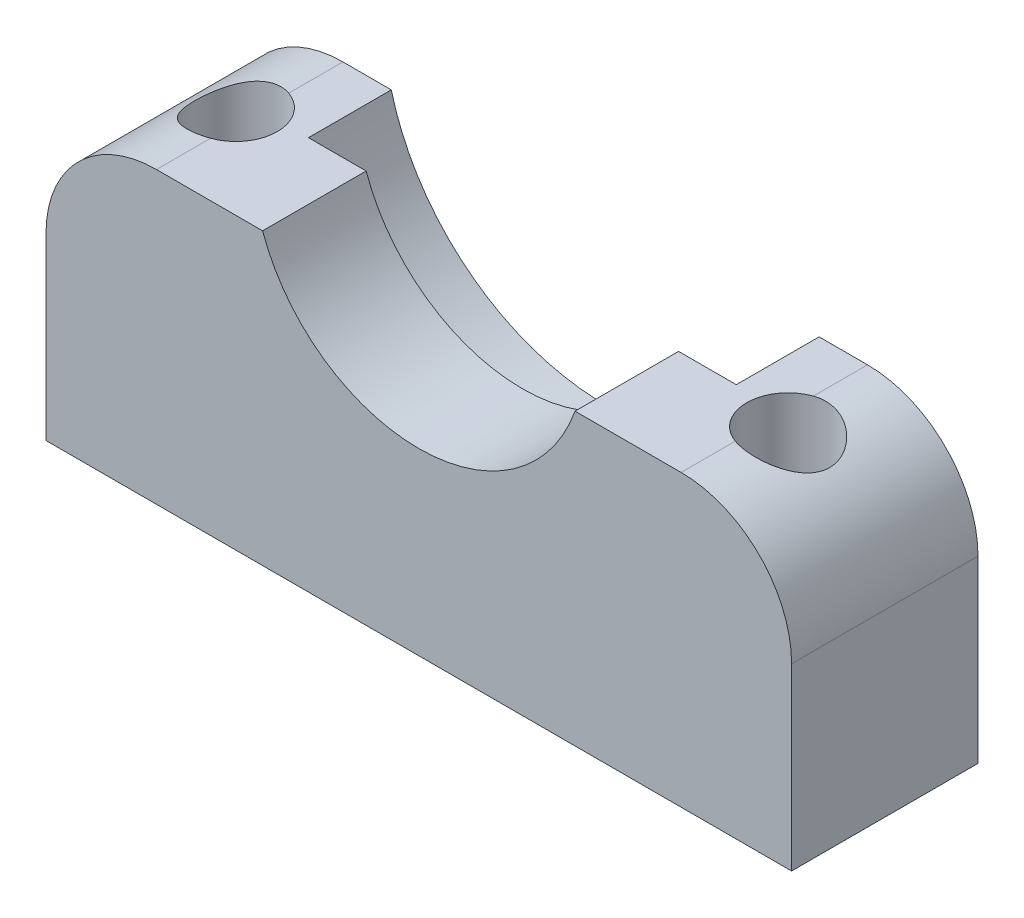
SolidWorks part; units mm, degrees
ref_plane "Front Plane" through (0, 0, 0) normal (0, 0, 1) x (1, 0, 0)
ref_plane "Top Plane" through (0, 0, 0) normal (0, 1, 0) x (1, 0, 0)
ref_plane "Right Plane" through (0, 0, 0) normal (1, 0, 0) x (0, 0, -1)
sketch "Sketch1" plane through (0, 0, 0) normal (0, 0, 1) x (1, 0, 0)
  line L1 (0, 0) -> (-27, 0)
  line L2 (0, 0) -> (0, 12.5)
  line L3 (0, 12.5) -> (-27, 12.5)
  line L4 (-27, 0) -> (-27, 12.5)
  circle A0 centre (-13.5, 12.5) radius 6
  dimension "D3" = 12
  dimension "D1" = 27
  dimension "D2" = 12.5
extrude "Boss-Extrude1" add sketch "Sketch1" along normal blind 6.75 contours A0 L3 L4 L1 L2 region at (-13.5, 5.5046, 0)
sketch "Sketch3" plane through (0, 0, 0) normal (0, 0, -1) x (-1, 0, 0)
  circle A0 centre (13.5, 12.5) radius 8
  dimension "D1" = 16
extrude "Cut-Extrude2" cut sketch "Sketch3" against normal blind 3
sketch "Sketch4" plane through (0, 0, 6.75) normal (0, 0, 1) x (1, 0, 0)
  line L0 (-27, 0) -> (-27, 12.5) construction
  line L1 (0, 12.5) -> (-27, 12.5)
  line L2 (0, 12.5) -> (0, 10.5)
  line L3 (0, 10.5) -> (-27, 10.5)
  line L4 (-27, 12.5) -> (-27, 10.5)
  line L5 (0, 0) -> (0, 12.5) construction
  line L6 (0, 12.5) -> (-7.5, 12.5) construction
  dimension "D1" = 2
extrude "Cut-Extrude3" cut sketch "Sketch4" against normal blind 9
sketch "Sketch5" plane through (0, 0, 0) normal (0, -1, 0) x (1, 0, 0)
  line L0 (-27, 3.375) -> (0, 3.375) construction
  line L1 (-27, 6.75) -> (-27, 0) construction
  line L2 (0, 6.75) -> (0, 0) construction
  circle A0 centre (-23.5, 3.375) radius 1.5
  circle A1 centre (-3.5, 3.375) radius 1.5
  point P10 (-1.6609, 4.5)
  dimension "D1" = 3
  dimension "D2" = 3.5
  dimension "D3" = 3.5
extrude "Cut-Extrude4" cut sketch "Sketch5" against normal blind 16
fillet "Fillet1" radius 4 2 edges at (-27, 10.5, 3.375) (0, 10.5, 3.375)
